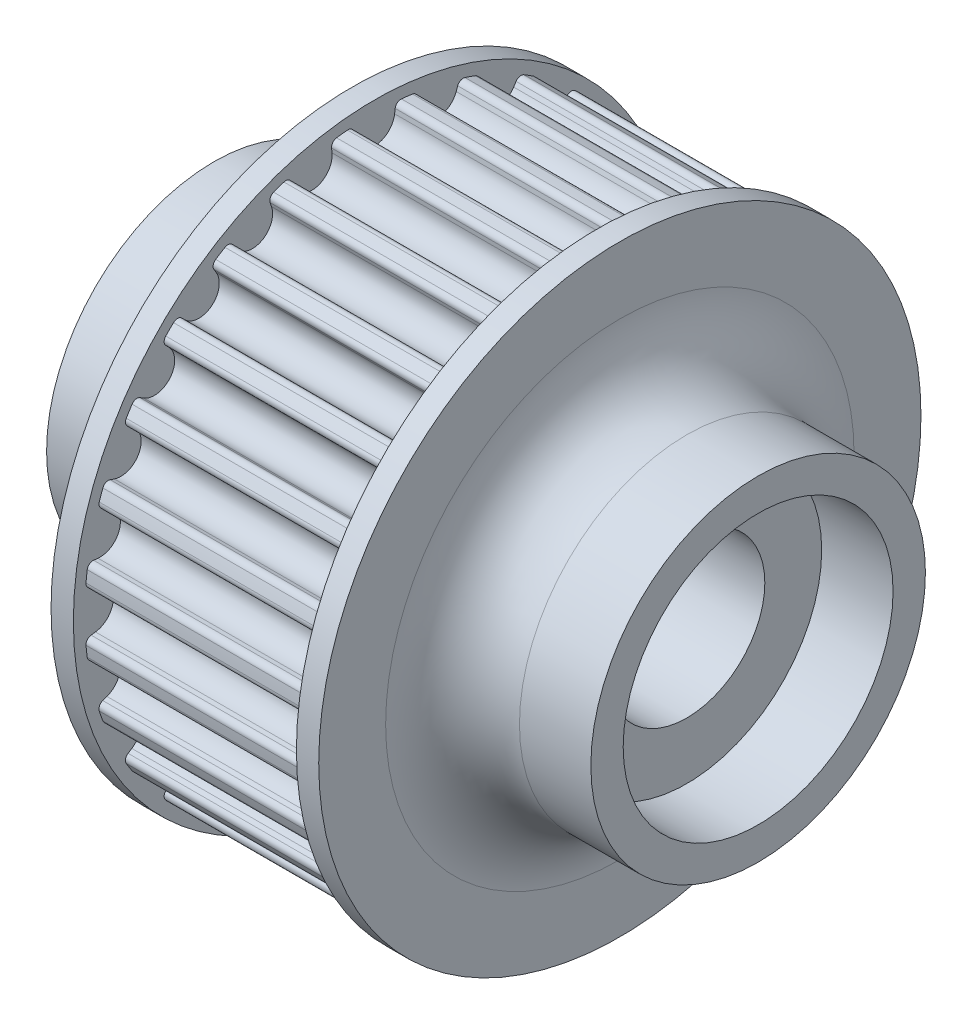
SolidWorks part; units mm, degrees
material "玻纤增强尼龙1010"
ref_plane "前视基准面" through (0, 0, 0) normal (0, 0, 1) x (1, 0, 0)
ref_plane "上视基准面" through (0, 0, 0) normal (0, 1, 0) x (1, 0, 0)
ref_plane "右视基准面" through (0, 0, 0) normal (1, 0, 0) x (0, 0, -1)
sketch "草图1" plane through (0, 0, 0) normal (0, 0, 1) x (1, 0, 0)
  line L0 (0, 0) -> (64.8368, 0) construction
  line L1 (0, 2.5978) -> (0, 12.989)
  line L2 (0, 12.989) -> (10, 12.989)
  line L3 (10, 12.989) -> (10, 5.1956)
  line L4 (10, 5.1956) -> (10.8, 5.1956)
  line L5 (10.8, 5.1956) -> (10.8, 2.5978)
  line L6 (10.8, 2.5978) -> (0, 2.5978)
  dimension "L" = 10.8
  dimension "B" = 10
  dimension "d" = 5.1956
  dimension "d1" = 10.3912
  dimension "da" = 25.978
revolve "旋转1" add sketch "草图1" angle 360 about L0
ref_axis "基准轴1" through (-0.54, 0, 0) along (1, 0, 0)
sketch "草图6" plane through (0, 0, 0) normal (1, 0, 0) x (0, 0, -1)
  line L0 (0, 0) -> (0, 30.6512) construction
  line L1 (0.9274, 12.7054) -> (0.9032, 12.5081)
  line L2 (1.4683, 12.9057) -> (1.665, 14.5073)
  line L3 (-1.4683, 12.9057) -> (-1.665, 14.5073)
  line L4 (-0.9274, 12.7054) -> (-0.9032, 12.5081)
  circle A0 centre (0, 0) radius 12.989 construction
  circle A1 centre (0, 0) radius 11.709 construction
  arc A2 (-0.9032, 12.5081) -> (0.9032, 12.5081) centre (0, 12.619) ccw
  arc A3 (1.665, 14.5073) -> (-1.665, 14.5073) centre (0, 0) ccw
  arc A4 (0.9274, 12.7054) -> (1.2097, 12.9325) centre (1.1855, 12.6737) cw
  arc A5 (1.2097, 12.9325) -> (1.4683, 12.9057) centre (0, 0) cw
  arc A6 (-1.2097, 12.9325) -> (-1.4683, 12.9057) centre (0, 0) ccw
  arc A7 (-0.9274, 12.7054) -> (-1.2097, 12.9325) centre (-1.1855, 12.6737) ccw
  point P7 (0, 1.9)
  point P8 (0, 29.3712)
  point P15 (0.9579, 12.9536)
  dimension "D1" = 23.418
  dimension "ra" = 0.26
  dimension "rf" = 0.91
  dimension "hg" = 1.28
  dimension "D3" = 0.26
  dimension "D4" = 1.6136
  dimension "angle" = 14
  dimension "bw" = 1.9
extrude "切除-拉伸2" cut sketch "草图6" along normal up to next
pattern_circular "阵列(圆周)3" count 28 over 360 about axis through (-0.54, 0, 0) along (1, 0, 0) of "切除-拉伸2"
sketch "草图7" plane through (0, 0, 0) normal (-1, 0, 0) x (0, 0, 1)
  circle A0 centre (0, 0) radius 2.5978
extrude "凸台-拉伸1" add sketch "草图7" against normal up to surface (10.8 mm away) up to face at (10.8, 0, 5.1956)
sketch "草图8" plane through (0, 0, 0) normal (-1, 0, 0) x (0, 0, 1)
  circle A0 centre (0, 0) radius 13.5
  dimension "D1" = 27
extrude "凸台-拉伸2" add sketch "草图8" along normal blind 1
sketch "草图9" plane through (10, 0, 0) normal (1, 0, 0) x (0, 0, -1)
  circle A0 centre (0, 0) radius 13.5
extrude "凸台-拉伸3" add sketch "草图9" along normal blind 1
sketch "草图10" plane through (-1, 0, 0) normal (-1, 0, 0) x (0, 0, 1)
  circle A0 centre (0, 0) radius 7.5
  dimension "D1" = 15
extrude "凸台-拉伸4" add sketch "草图10" along normal blind 6.2
sketch "草图11" plane through (11, 0, 0) normal (1, 0, 0) x (0, 0, -1)
  circle A0 centre (0, 0) radius 7.5
  dimension "D1" = 15
extrude "凸台-拉伸5" add sketch "草图11" along normal blind 6.2
sketch "草图12" plane through (-7.2, 0, 0) normal (-1, 0, 0) x (0, 0, 1)
  circle A0 centre (0, 0) radius 3.5
  dimension "D1" = 7
extrude "切除-拉伸3" cut sketch "草图12" against normal blind 31
fillet "圆角1" radius 3 2 edges at (11, 0, -7.5) (-1, 0, 7.5)
sketch "草图13" plane through (17.2, 0, 0) normal (1, 0, 0) x (0, 0, -1)
  circle A0 centre (0, 0) radius 6.05
  dimension "D1" = 12.1
extrude "切除-拉伸4" cut sketch "草图13" against normal blind 3.2
sketch "草图14" plane through (-7.2, 0, 0) normal (-1, 0, 0) x (0, 0, 1)
  circle A0 centre (0, 0) radius 6.05
  dimension "D1" = 12.1
extrude "切除-拉伸5" cut sketch "草图14" against normal blind 3.2
equation "\"D1@草图6\" = \"da@草图1\"  - \"hg@草图6\" - \"hg@草图6\""
equation "\"D3@草图6\" = \"ra@草图6\""
